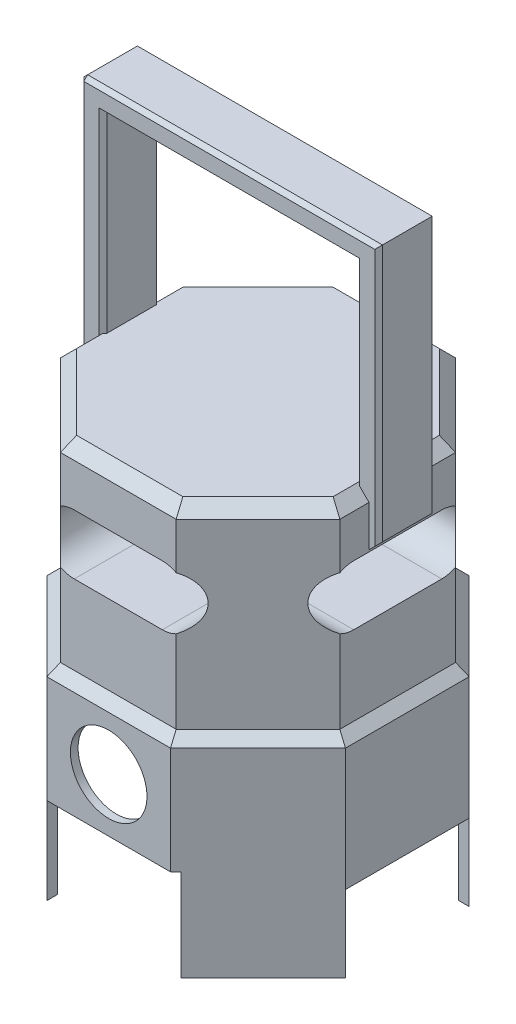
SolidWorks part; units mm, degrees
ref_plane "Front Plane" through (0, 0, 0) normal (0, 0, 1) x (1, 0, 0)
ref_plane "Top Plane" through (0, 0, 0) normal (0, 1, 0) x (1, 0, 0)
ref_plane "Right Plane" through (0, 0, 0) normal (1, 0, 0) x (0, 0, -1)
sketch "Sketch1" plane through (0, 0, 0) normal (0, 1, 0) x (1, 0, 0)
  line L1 (15.1188, 36.5) -> (-15.1188, 36.5)
  line L2 (-15.1188, 36.5) -> (-36.5, 15.1188)
  line L3 (-36.5, 15.1188) -> (-36.5, -15.1188)
  line L4 (-36.5, -15.1188) -> (-15.1188, -36.5)
  line L5 (-15.1188, -36.5) -> (15.1188, -36.5)
  line L6 (15.1188, -36.5) -> (36.5, -15.1188)
  line L7 (36.5, -15.1188) -> (36.5, 15.1188)
  line L8 (36.5, 15.1188) -> (15.1188, 36.5)
  circle A0 centre (0, 0) radius 36.5 construction
  dimension "D1" = 73
extrude "Boss-Extrude1" add sketch "Sketch1" along normal blind 50
sketch "Sketch7" plane through (0, 0, 0) normal (0, -1, 0) x (1, 0, 0)
  line L0 (-15.1188, 36.5) -> (15.1188, 36.5) construction
  line L1 (39, 16.1543) -> (16.1543, 39)
  line L2 (16.1543, 39) -> (-16.1543, 39)
  line L3 (-16.1543, 39) -> (-39, 16.1543)
  line L4 (-39, 16.1543) -> (-39, -16.1543)
  line L5 (-39, -16.1543) -> (-16.1543, -39)
  line L6 (-16.1543, -39) -> (16.1543, -39)
  line L7 (16.1543, -39) -> (39, -16.1543)
  line L8 (39, -16.1543) -> (39, 16.1543)
  circle A0 centre (0, 0) radius 39 construction
  dimension "76" = 78
extrude "Boss-Extrude4" add sketch "Sketch7" along normal blind 55
sketch "Sketch18" plane through (0, 50, 0) normal (0, 1, 0) x (1, 0, 0)
  line L0 (-39, -16.1543) -> (-39, 16.1543) construction
  line L2 (-39, 7.5) -> (-39, -7.5)
  line L12 (-39, 7.5) -> (-33, 7.5)
  line L14 (-33, 7.5) -> (-33, -7.5)
  line L15 (-33, -7.5) -> (-39, -7.5)
  line L16 (0, -55) -> (0, 55) construction
  line L17 (33, 7.5) -> (33, -7.5)
  line L18 (39, 7.5) -> (33, 7.5)
  line L19 (39, 7.5) -> (39, -7.5)
  line L20 (33, -7.5) -> (39, -7.5)
  point P1 (-33, 0)
  dimension "D1" = 15
  dimension "D2" = 6
  dimension "D3" = 6
sketch "Sketch3" plane through (0, 0, 36.5) normal (0, 0, 1) x (1, 0, 0)
  line L0 (-11.5, 28) -> (11.5, 28) construction
  line L1 (-11.5, 35.8) -> (11.5, 35.8)
  line L2 (-11.5, 20.2) -> (11.5, 20.2)
  line L4 (-15.1188, 50) -> (15.1188, 50) construction
  arc A0 (-11.5, 35.8) -> (-11.5, 20.2) centre (-11.5, 28) ccw
  arc A1 (11.5, 20.2) -> (11.5, 35.8) centre (11.5, 28) ccw
  point P2 (0, 28)
  dimension "D1" = 7.8
  dimension "D2" = 23
  dimension "D3" = 22
extrude "Cut-Extrude1" cut sketch "Sketch3" against normal up to surface (73 mm away) up to face at (0, 25, -36.5)
sketch "Sketch4" plane through (-36.5, 0, 0) normal (-1, 0, 0) x (0, 0, 1)
  line L0 (-11.5, 28) -> (11.5, 28) construction
  line L1 (-11.5, 35.8) -> (11.5, 35.8)
  line L2 (-11.5, 20.2) -> (11.5, 20.2)
  line L4 (-15.1188, 50) -> (15.1188, 50) construction
  arc A0 (-11.5, 35.8) -> (-11.5, 20.2) centre (-11.5, 28) ccw
  arc A1 (11.5, 20.2) -> (11.5, 35.8) centre (11.5, 28) ccw
  point P2 (0, 28)
  dimension "D1" = 7.8
  dimension "D2" = 22
  dimension "D3" = 23
extrude "Cut-Extrude2" cut sketch "Sketch4" against normal up to surface and the other way up to surface up to face at (39, -27.5, 0) other way up to face at (-39, -27.5, 0)
chamfer "Chamfer5" distance 3 angle 45 8 edges at (-39, 0, 0) (-27.5772, 0, -27.5772) (0, 0, -39) (27.5772, 0, -27.5772) (39, 0, 0) (27.5772, 0, 27.5772) (0, 0, 39) (-27.5772, 0, 27.5772)
shell "Shell1" thickness 2 removed face at (0, -55, 0)
sketch "Sketch11" plane through (0, 0, -39) normal (0, 0, 1) x (1, 0, 0)
  line L1 (16.1543, -55) -> (-16.1543, -55) construction
  circle A0 centre (0, -17) radius 10
  dimension "D2" = 20
  dimension "D1" = 38
extrude "Cut-Extrude5" cut sketch "Sketch11" along normal up to surface (78 mm away) up to face at (0, -29, 39)
chamfer "Chamfer7" distance 3 angle 45 8 edges at (25.8094, 50, 25.8094) (0, 50, 36.5) (-25.8094, 50, 25.8094) (36.5, 50, 0) (25.8094, 50, -25.8094) (-36.5, 50, 0) (-25.8094, 50, -25.8094) (0, 50, -36.5)
extrude "Boss-Extrude10" add sketch "Sketch18" along normal blind 50 and the other way up to surface (14.2 mm away) separate body other way up to face at (0, 35.8, 0)
sketch "Sketch20" plane through (0, 100, 0) normal (0, 1, 0) x (1, 0, 0)
  line L1 (-39, 7.5) -> (39, 7.5)
  line L2 (-39, 7.5) -> (-39, -7.5)
  line L3 (-39, -7.5) -> (39, -7.5)
  line L4 (39, 7.5) -> (39, -7.5)
extrude "Boss-Extrude11" add sketch "Sketch20" along normal blind 6
chamfer "Chamfer8" distance 3 angle 45 2 edges at (-39, 35.8, 0) (39, 35.8, 0)
chamfer "Chamfer9" distance 1 angle 45 13 edges at (-33, 67.9, -7.5) (0, 100, -7.5) (33, 67.9, -7.5) (-33, 67.9, 7.5) (0, 100, 7.5) (33, 67.9, 7.5) (39, 72.4, -7.5) (0, 106, -7.5) (-39, 72.4, -7.5) (-39, 106, 0) (39, 72.4, 7.5) (0, 106, 7.5) (-39, 72.4, 7.5)
sketch "Sketch21" plane through (0, 0, 39) normal (0, 0, 1) x (1, 0, 0)
  line L0 (39, -55) -> (16.1543, -55) construction
  line L1 (-17.5, -31) -> (17.5, -31)
  line L2 (-17.5, -31) -> (-17.5, -55)
  line L3 (-17.5, -55) -> (17.5, -55)
  line L4 (17.5, -31) -> (17.5, -55)
  point P6 (0, -31)
  dimension "D1" = 35
  dimension "D2" = 24
extrude "Cut-Extrude6" cut sketch "Sketch21" against normal up to surface (78 mm away) up to face at (10, -17, -39)
sketch "Sketch22" plane through (-39, 0, 0) normal (-1, 0, 0) x (0, 0, 1)
  line L0 (-16.1543, -55) -> (-16.1543, -3) construction
  line L1 (-16.1543, -35) -> (16.1543, -35)
  line L2 (-16.1543, -35) -> (-16.1543, -55)
  line L3 (-16.1543, -55) -> (16.1543, -55)
  line L4 (16.1543, -35) -> (16.1543, -55)
  dimension "D1" = 20
extrude "Cut-Extrude7" cut sketch "Sketch22" against normal up to surface (78 mm away) up to face at (39, -29, 0)
